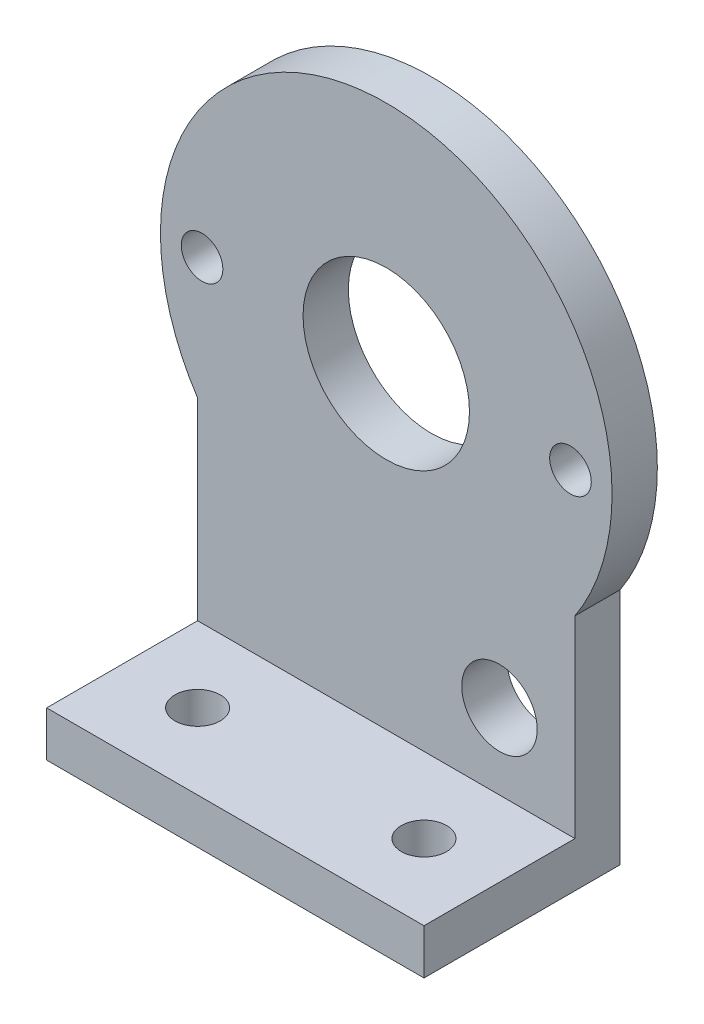
SolidWorks part; units mm, degrees
ref_plane "Front Plane" through (0, 0, 0) normal (0, 0, 1) x (1, 0, 0)
ref_plane "Top Plane" through (0, 0, 0) normal (0, 1, 0) x (1, 0, 0)
ref_plane "Right Plane" through (0, 0, 0) normal (1, 0, 0) x (0, 0, -1)
sketch "Sketch1" plane through (0, 0, 0) normal (0, 0, 1) x (1, 0, 0)
  line L1 (-15.875, -10.4396) -> (15.875, -10.4396)
  line L2 (-15.875, -10.4396) -> (-15.875, -30.48)
  line L3 (-15.875, -30.48) -> (15.875, -30.48)
  line L4 (15.875, -10.4396) -> (15.875, -30.48)
  circle A0 centre (0, 0) radius 19
  arc A2 (-15.875, -10.4396) -> (15.875, -10.4396) centre (0, 0) ccw
  dimension "D1" = 38
  dimension "D2" = 30.48
  dimension "D3" = 31.75
extrude "Boss-Extrude1" add sketch "Sketch1" along normal blind 3.81 contours A0 | L2 L1 L4 L3
sketch "Sketch3" plane through (0, 0, 3.81) normal (0, 0, 1) x (1, 0, 0)
  circle A0 centre (0, 0) radius 7
  dimension "D1" = 14
extrude "Cut-Extrude1" cut sketch "Sketch3" against normal through all
sketch "Sketch4" plane through (0, 0, 3.81) normal (0, 0, 1) x (1, 0, 0)
  line L0 (15.875, -10.4396) -> (15.875, -30.48) construction
  line L1 (-15.875, -30.48) -> (15.875, -30.48)
  line L2 (-15.875, -30.48) -> (-15.875, -26.67)
  line L3 (-15.875, -26.67) -> (15.875, -26.67)
  line L4 (15.875, -30.48) -> (15.875, -26.67)
  dimension "D1" = 3.81
extrude "Boss-Extrude2" add sketch "Sketch4" along normal blind 12.7
sketch "Sketch5" plane through (0, -26.67, 0) normal (0, 1, 0) x (1, 0, 0)
  line L0 (-15.875, -10.16) -> (15.875, -10.16) construction
  line L1 (-15.875, -16.51) -> (-15.875, -3.81) construction
  line L2 (15.875, -16.51) -> (15.875, -3.81) construction
  line L3 (0, -3.81) -> (0, -16.51) construction
  line L4 (15.875, -3.81) -> (-15.875, -3.81) construction
  line L5 (15.875, -16.51) -> (-15.875, -16.51) construction
  circle A0 centre (-9.525, -10.16) radius 1.905
  circle A1 centre (9.525, -10.16) radius 1.905
  dimension "D1" = 3.81
  dimension "D2" = 9.525
extrude "Cut-Extrude2" cut sketch "Sketch5" against normal through all
sketch "Sketch6" plane through (0, 0, 3.81) normal (0, 0, 1) x (1, 0, 0)
  line L0 (0, 19) -> (0, -26.67) construction
  line L1 (15.875, -26.67) -> (-15.875, -26.67) construction
  circle A0 centre (0, 0) radius 15.5 construction
  circle A1 centre (15.5, 0) radius 1.75
  arc A2 (15.875, -10.4396) -> (-15.875, -10.4396) centre (0, 0) ccw construction
  circle A3 centre (-15.5, 0) radius 1.75
  dimension "D1" = 31
  dimension "D2" = 3.5
extrude "Cut-Extrude3" cut sketch "Sketch6" against normal through all
sketch "Sketch7" plane through (0, 0, 3.81) normal (0, 0, 1) x (1, 0, 0)
  line L0 (15.875, -10.4396) -> (15.875, -26.67) construction
  line L1 (15.875, -26.67) -> (-15.875, -26.67) construction
  circle A0 centre (9.525, -20.32) radius 3.175
  dimension "D1" = 6.35
  dimension "D2" = 6.35
  dimension "D3" = 6.35
extrude "Cut-Extrude4" cut sketch "Sketch7" against normal through all
